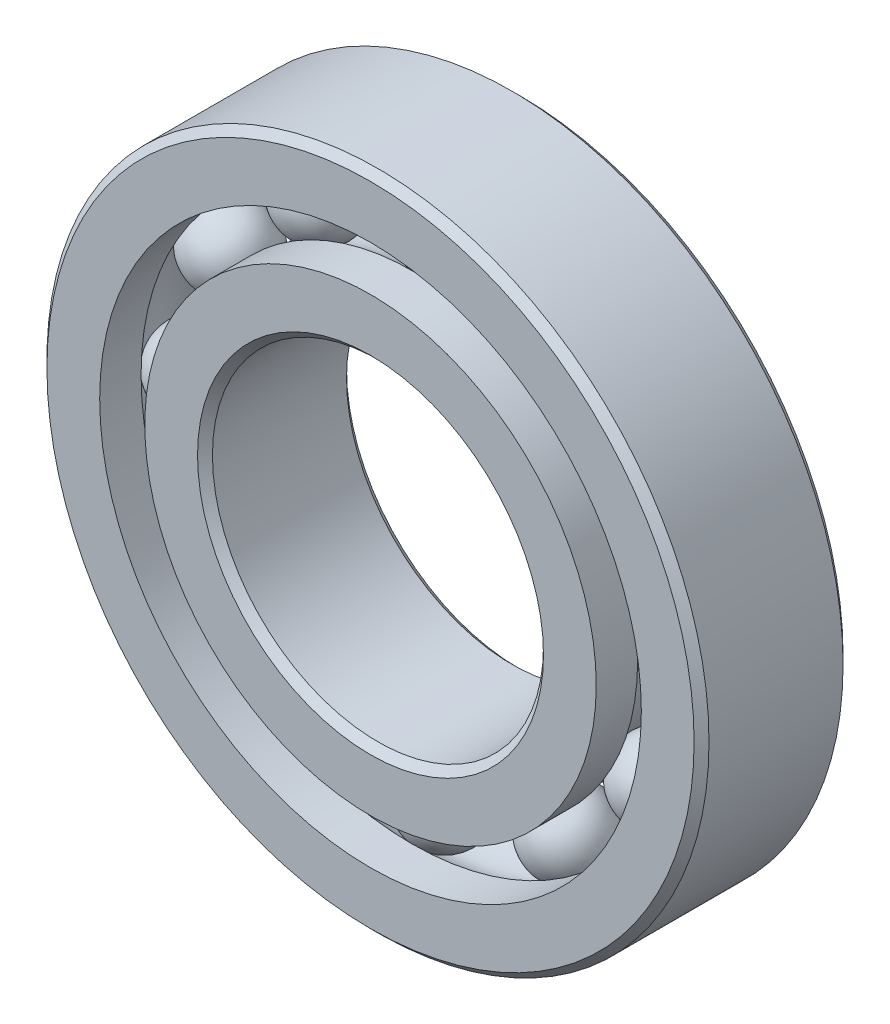
SolidWorks part; units mm, degrees
ref_plane "Front Plane" through (0, 0, 0) normal (0, 0, 1) x (1, 0, 0)
ref_plane "Top Plane" through (0, 0, 0) normal (0, 1, 0) x (1, 0, 0)
ref_plane "Right Plane" through (0, 0, 0) normal (1, 0, 0) x (0, 0, -1)
sketch "Sketch1" plane through (0, 0, 0) normal (1, 0, 0) x (0, 0, -1)
  line L0 (-9, 0) -> (9, 0) construction
  line L1 (0, 40) -> (0, -40) construction
  line L2 (8.1, 40) -> (-8.1, 40)
  line L3 (-8.1, 40) -> (-9, 39.1)
  line L4 (-9, 39.1) -> (-9, 32.7253)
  line L5 (-9, 32.7253) -> (-4, 32.7253)
  line L6 (9, 32.7253) -> (4, 32.7253)
  line L7 (9, 39.1) -> (9, 32.7253)
  line L8 (8.1, 40) -> (9, 39.1)
  line L9 (0, 40) -> (0, 30) construction
  line L10 (0, 30) -> (0, 20) construction
  arc A0 (-4, 32.7253) -> (4, 32.7253) centre (0, 30) cw
  point P14 (0, 20)
  dimension "D3" = 8
  dimension "D1" = 45
  dimension "Width" = 18
  dimension "OD" = 80
  dimension "D2" = 0.9
  dimension "Shaft Dia" = 40
  dimension "D4" = 2.7253
revolve "Revolve1" add sketch "Sketch1" angle 360 about L0
sketch "Sketch3" plane through (0, 0, 0) normal (1, 0, 0) x (0, 0, -1)
  line L0 (-9, 27.2747) -> (-4, 27.2747)
  line L1 (0, 40) -> (0, -40) construction
  line L2 (-9, 39.1) -> (-9, 32.7253) construction
  line L3 (-9, 27.2747) -> (-9, 20.9)
  line L4 (-8.1, 40) -> (-9, 39.1) construction
  line L5 (-9, 20.9) -> (-8.1, 20)
  line L6 (-8.1, 20) -> (8.1, 20)
  line L7 (8.1, 40) -> (8.1, -40) construction
  line L8 (8.1, 20) -> (9, 20.9)
  line L9 (9, -39.1) -> (9, 39.1) construction
  line L10 (9, 20.9) -> (9, 27.2747)
  line L11 (9, 27.2747) -> (4, 27.2747)
  line L13 (8.1, 40) -> (9, 39.1) construction
  arc A0 (4, 32.7253) -> (-4, 32.7253) centre (0, 30) ccw construction
  arc A1 (4, 27.2747) -> (-4, 27.2747) centre (0, 30) cw
revolve "Revolve3" add sketch "Sketch3" angle 360 about L0
sketch "Sketch4" plane through (0, 0, 0) normal (1, 0, 0) x (0, 0, -1)
  line L0 (-4.8402, 30) -> (4.8402, 30)
  arc A2 (-4.8402, 30) -> (4.8402, 30) centre (0, 30) cw
  arc A3 (4, 32.7253) -> (-4, 32.7253) centre (0, 30) ccw construction
revolve "Revolve4" add sketch "Sketch4" angle 360 about L0
ref_axis "Axis1" through (0, 0, -9) along (0, 0, 1)
pattern_circular "CirPattern1" count 12 every 30 about axis through (0, 0, -9) along (0, 0, 1) of bodies 104
sketch "Sketch5" plane through (0, 0, 0) normal (1, 0, 0) x (0, 0, -1)
  line L0 (-9, 32.7253) -> (-4, 32.7253) construction
  line L1 (-8.55, 32.7253) -> (-4.8402, 32.7253)
  line L2 (-8.55, 32.7253) -> (-8.55, 27.2747)
  line L3 (-8.55, 27.2747) -> (-4.8402, 27.2747)
  line L4 (-4.8402, 32.7253) -> (-4.8402, 27.2747)
  line L5 (-9, 27.2747) -> (-4, 27.2747) construction
  line L6 (9, 32.7253) -> (4, 32.7253) construction
  line L7 (8.55, 32.7253) -> (4.8402, 32.7253)
  line L8 (8.55, 32.7253) -> (8.55, 27.2747)
  line L9 (8.55, 27.2747) -> (4.8402, 27.2747)
  line L10 (4.8402, 32.7253) -> (4.8402, 27.2747)
  line L11 (9, 27.2747) -> (4, 27.2747) construction
  line L12 (-8.1, 40) -> (-9, 39.1) construction
  point P18 (-8.55, 39.55)
revolve "Revolve5" [suppressed] add sketch "Sketch5" angle 360 about L0
equation "\"D2@Sketch1\" = \"Width@Sketch1\"*.05"
equation "\"D3@Sketch1\" = \"Width@Sketch1\"/2.25"
equation "\"D4@Sketch1\" = (((\"OD@Sketch1\"-\"Width@Sketch1\")/2)/3.25)/3.5"
equation "\"D2@CirPattern1\" = 360/\"Balls@CirPattern1\""
